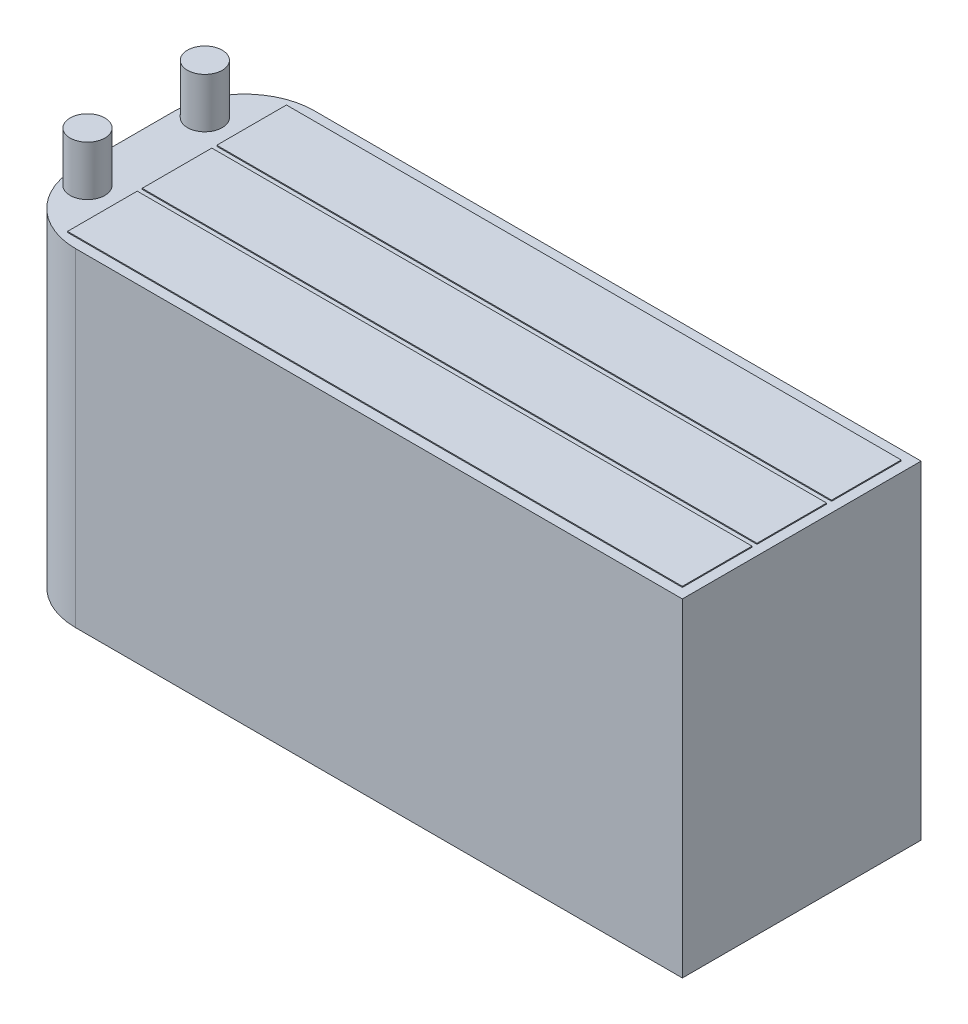
SolidWorks part; units mm, degrees
ref_plane "Front Plane" through (0, 0, 0) normal (0, 0, 1) x (1, 0, 0)
ref_plane "Top Plane" through (0, 0, 0) normal (0, 1, 0) x (1, 0, 0)
ref_plane "Right Plane" through (0, 0, 0) normal (1, 0, 0) x (0, 0, -1)
sketch "Sketch1" plane through (0, 0, 0) normal (0, 0, 1) x (1, 0, 0)
  line L1 (-34, -16.5) -> (34, -16.5)
  line L2 (-34, -16.5) -> (-34, 16.5)
  line L3 (-34, 16.5) -> (34, 16.5)
  line L4 (34, -16.5) -> (34, 16.5)
  line L5 (-34, -16.5) -> (34, 16.5) construction
  line L6 (-34, 16.5) -> (34, -16.5) construction
  point P0 (0, 0)
  dimension "D1" = 68
  dimension "D2" = 33
extrude "Boss-Extrude1" add sketch "Sketch1" along normal blind 24
fillet "Fillet1" radius 7 2 edges at (-34, 0, 0) (-34, 0, 24)
sketch "Sketch2" plane through (0, 16.5, 0) normal (0, 1, 0) x (1, 0, 0)
  line L0 (33, -19.5) -> (34, -19.5) construction
  line L1 (33, -1) -> (-28.8, -1)
  line L2 (33, -1) -> (33, -8)
  line L3 (33, -8) -> (-28.8, -8)
  line L4 (-28.8, -1) -> (-28.8, -8)
  line L5 (33, -8.5) -> (-28.8, -8.5)
  line L6 (33, -8.5) -> (33, -15.5)
  line L7 (33, -15.5) -> (-28.8, -15.5)
  line L8 (-28.8, -8.5) -> (-28.8, -15.5)
  line L9 (-28.8, -16) -> (33, -16)
  line L10 (-28.8, -16) -> (-28.8, -23)
  line L11 (-28.8, -23) -> (33, -23)
  line L12 (33, -16) -> (33, -23)
  line L13 (34, -24) -> (34, 0) construction
  line L14 (33, -12) -> (34, -12) construction
  line L15 (33, -4.5) -> (34, -4.5) construction
  line L16 (34, -4.5) -> (34, -12) construction
  line L17 (34, -12) -> (34, -19.5) construction
  line L18 (2.1, -8.5) -> (2.1, -8) construction
  line L19 (2.1, -15.5) -> (2.1, -16) construction
  line L20 (2.1, -1) -> (2.1, 0) construction
  line L21 (34, 0) -> (-27, 0) construction
  line L22 (2.1, -23) -> (2.1, -24) construction
  line L23 (34, -24) -> (-27, -24) construction
  dimension "D1" = 0.5
  dimension "D2" = 1
  dimension "D3" = 1
extrude "Boss-Extrude2" add sketch "Sketch2" along normal blind 0.1 separate body
mirror "Mirror1" about plane through (0, 0, 0) normal (0, 1, 0) of bodies 115 120 119 117
sketch "Sketch3" plane through (0, 16.5, 0) normal (0, 1, 0) x (1, 0, 0)
  line L0 (-31.9, -6.1) -> (-31.9, -17.9) construction
  line L1 (-34, -12) -> (-31.9, -12) construction
  line L2 (-34, -17) -> (-34, -7) construction
  circle A0 centre (-31.9, -6.1) radius 1.75
  circle A1 centre (-31.9, -17.9) radius 1.75
  dimension "D1" = 3.5
extrude "Boss-Extrude3" add sketch "Sketch3" along normal blind 5
